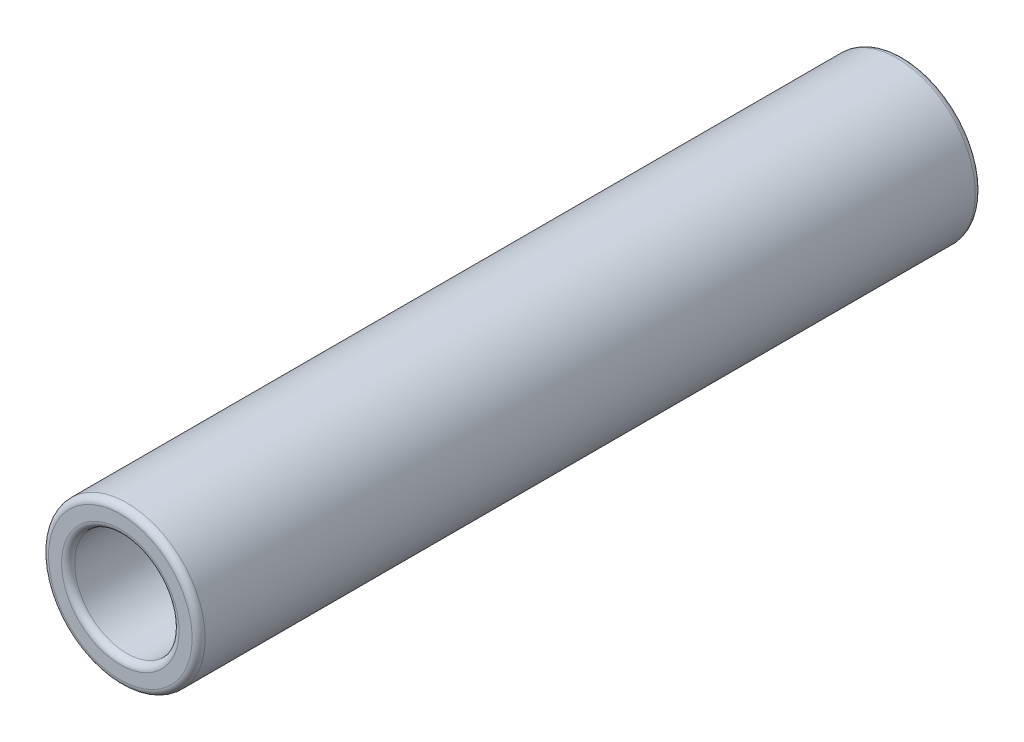
SolidWorks part; units mm, degrees
ref_plane "Front Plane" through (0, 0, 0) normal (0, 0, 1) x (1, 0, 0)
ref_plane "Top Plane" through (0, 0, 0) normal (0, 1, 0) x (1, 0, 0)
ref_plane "Right Plane" through (0, 0, 0) normal (1, 0, 0) x (0, 0, -1)
sketch "Sketch1" plane through (0, 0, 0) normal (0, 0, 1) x (1, 0, 0)
  circle A0 centre (0, 0) radius 4
  circle A1 centre (0, 0) radius 6
  dimension "D1" = 8
  dimension "D2" = 12
extrude "Boss-Extrude1" add sketch "Sketch1" along normal mid plane 60
fillet "Fillet1" radius 0.5 4 edges at (4, 0, -30) (4, 0, 30) (6, 0, -30) (6, 0, 30)
